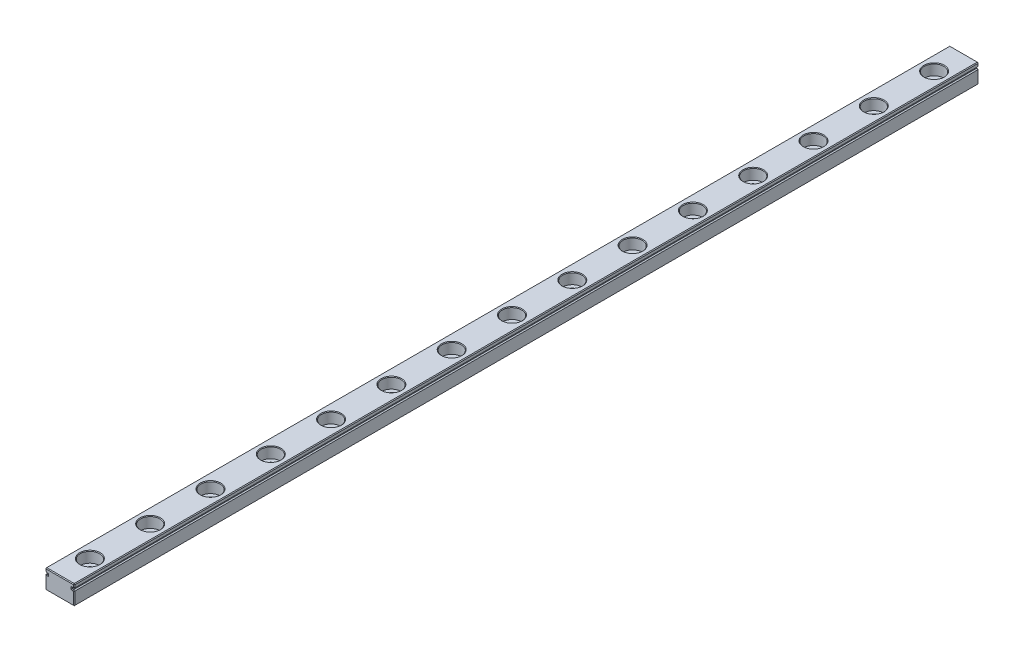
SolidWorks part; units mm, degrees
material "AISI 304"
ref_plane "Front Plane" through (0, 0, 0) normal (0, 0, 1) x (1, 0, 0)
ref_plane "Top Plane" through (0, 0, 0) normal (0, 1, 0) x (1, 0, 0)
ref_plane "Right Plane" through (0, 0, 0) normal (1, 0, 0) x (0, 0, -1)
sketch "Sketch1" plane through (0, 0, 0) normal (0, 0, 1) x (1, 0, 0)
  line L0 (0, 0) -> (0, 8) construction
  line L1 (0, 8) -> (12, 8)
  line L2 (0, 0) -> (12, 0)
  line L3 (0, 8) -> (0, 6.75)
  line L4 (0, 6.75) -> (0.5, 6.25) construction
  line L5 (0.5, 6.25) -> (1, 6.25)
  line L6 (0.5, 5.75) -> (0, 5.25) construction
  line L7 (0, 5.25) -> (0, 0)
  line L8 (1, 6.25) -> (1, 5.75)
  line L9 (1, 5.75) -> (0.5, 5.75)
  line L10 (0.5, 5.75) -> (0.75, 6) construction
  line L11 (0.75, 6) -> (0.5, 6.25) construction
  line L12 (0, 6.75) -> (0, 6.559)
  line L13 (0, 5.25) -> (0, 5.441)
  line L14 (6, 8) -> (6, 0) construction
  line L15 (11.25, 6) -> (11.5, 6.25) construction
  line L16 (11.5, 5.75) -> (11.25, 6) construction
  line L17 (11.5, 5.75) -> (12, 5.25) construction
  line L18 (12, 6.75) -> (11.5, 6.25) construction
  line L19 (12, 0) -> (12, 8) construction
  line L20 (12, 5.25) -> (12, 5.441)
  line L21 (12, 6.75) -> (12, 6.559)
  line L22 (11, 5.75) -> (11.5, 5.75)
  line L23 (11, 6.25) -> (11, 5.75)
  line L24 (12, 5.25) -> (12, 0)
  line L25 (11.5, 6.25) -> (11, 6.25)
  line L26 (12, 8) -> (12, 6.75)
  arc A0 (0, 5.441) -> (0.5, 5.75) centre (0, 6) ccw
  arc A1 (0.5, 6.25) -> (0, 6.559) centre (0, 6) ccw
  arc A2 (11.5, 6.25) -> (12, 6.559) centre (12, 6) cw
  arc A3 (12, 5.441) -> (11.5, 5.75) centre (12, 6) cw
  point P4 (1, 6)
  point P28 (11, 6)
  dimension "D1" = 8
  dimension "D2" = 6
  dimension "D3" = 0.5
  dimension "D4" = 45
  dimension "D5" = 2
  dimension "D6" = 1
extrude "Boss-Extrude1" add sketch "Sketch1" along normal blind 375
chamfer "Chamfer1" distance 0.3 angle 45 36 edges at (0, 0, 187.5) (12, 0, 187.5) (0, 8, 187.5) (12, 8, 187.5) (0.2939, 5.5245, 375) (0.75, 5.75, 375) (1, 6, 375) (0.75, 6.25, 375) (0.2939, 6.4755, 375) (0, 7.2795, 375) (6, 8, 375) (12, 7.2795, 375) (11.7061, 6.4755, 375) (11.25, 6.25, 375) (11, 6, 375) (11.25, 5.75, 375) (11.7061, 5.5245, 375) (12, 2.7205, 375) (6, 0, 375) (0, 2.7205, 375) (12, 2.7205, 0) (11.7061, 5.5245, 0) (11.25, 5.75, 0) (11, 6, 0) (11.25, 6.25, 0) (11.7061, 6.4755, 0) (12, 7.2795, 0) (6, 0, 0) (0, 2.7205, 0) (0.2939, 5.5245, 0) (0.75, 5.75, 0) (1, 6, 0) (0.75, 6.25, 0) (0.2939, 6.4755, 0) (0, 7.2795, 0) (6, 8, 0)
hole_wizard "CBORE for M5 Hex Head Bolt1" positions "3DSketch1" profile "Sketch3" counterbore size "M5" standard "ANSI Metric" end condition through all
sketch3d "3DSketch1"
  line L0 (6, 8, 0) -> (6, 8, 12.5) construction
  line L1 (11.7, 8, 0) -> (0.3, 8, 0) construction
  point P0 (6, 8, 12.5)
  dimension "D1" = 12.5
sketch "Sketch3" plane through (6, 8, 12.5) normal (1, 0, 0) x (0, 0, 1)
  line L0 (0, 0) -> (0, 8)
  line L1 (2.25, 7.75) -> (2.5, 8)
  line L2 (4, 4.5) -> (2.25, 4.5)
  line L3 (2.25, 4.5) -> (2.25, 7.75)
  line L5 (4, 4.5) -> (4, 0.25)
  line L6 (4, 0.25) -> (4.25, 0)
  line L7 (4.25, 0) -> (0, 0)
  line L8 (-4, 0.25) -> (-4.25, 0) construction
  line L11 (0, -6.35) -> (0, 107.95) construction
  line L12 (2.5, 8) -> (0, 8)
  line L13 (-2.25, 7.75) -> (-2.5, 8) construction
  dimension "Thru Hole Dia." = 4.5
  dimension "Thru Hole Depth" = 8
  dimension "C'Bore Dia." = 8
  dimension "C'Bore Depth" = 4.5
  dimension "Near C'Sink Dia." = 8.5
  dimension "Near C'Sink Angle" = 90
  dimension "Far C'Sink Dia." = 5
  dimension "Far C'Sink Angle" = 90
pattern_linear "LPattern1" count 15 spacing 25 along (0, 0, 1) of "CBORE for M5 Hex Head Bolt1"
